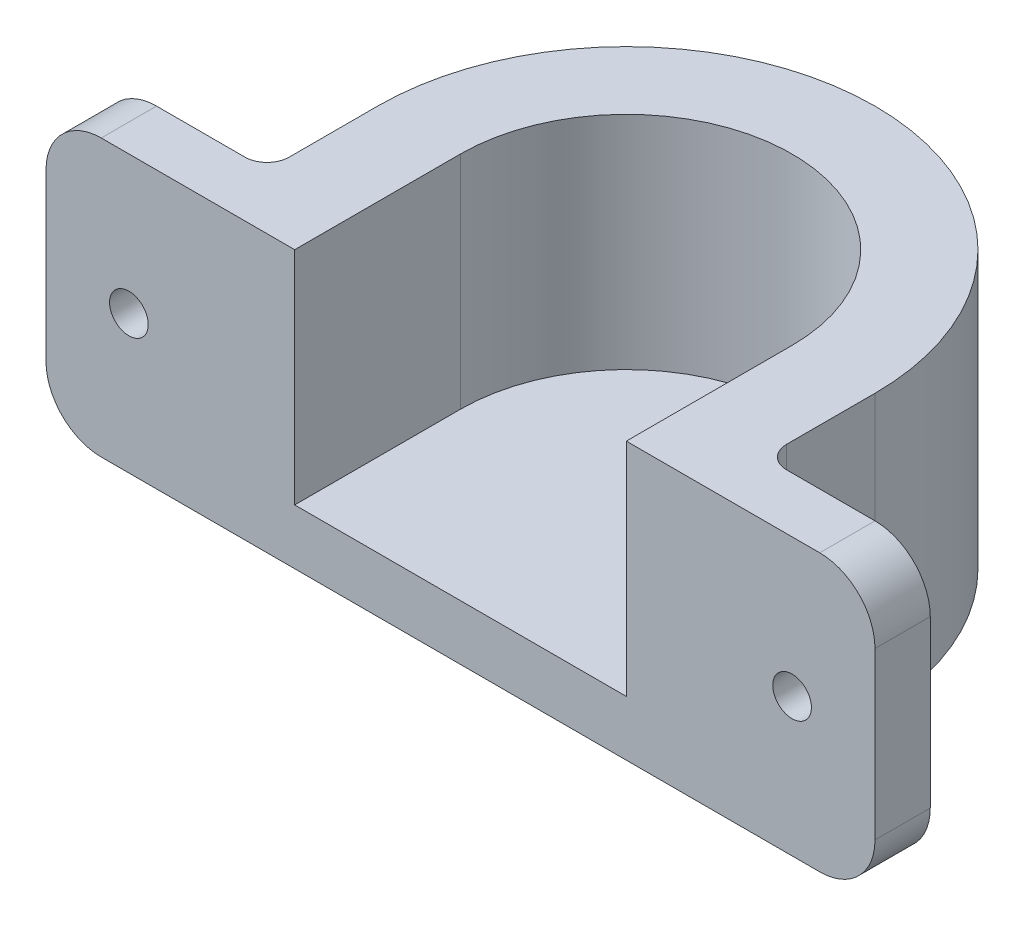
SolidWorks part; units mm, degrees
ref_plane "Front Plane" through (0, 0, 0) normal (0, 0, 1) x (1, 0, 0)
ref_plane "Top Plane" through (0, 0, 0) normal (0, 1, 0) x (1, 0, 0)
ref_plane "Right Plane" through (0, 0, 0) normal (1, 0, 0) x (0, 0, -1)
sketch "Sketch1" plane through (0, 0, 0) normal (0, 1, 0) x (1, 0, 0)
  line L0 (-7.5, 0) -> (-7.5, -10)
  line L1 (-7.5, -10) -> (-22.5, -10)
  line L2 (-22.5, -10) -> (-22.5, -15)
  line L3 (-22.5, -15) -> (0, -15)
  line L4 (0, -15) -> (0, 0)
  line L5 (-7.5, 0) -> (0, 0) construction
  line L6 (15, 0) -> (30, 0) construction
  line L7 (30, 0) -> (37.5, 0) construction
  line L8 (0, 0) -> (15, 0) construction
  line L9 (30, 0) -> (30, -15)
  line L10 (30, -15) -> (52.5, -15)
  line L11 (52.5, -15) -> (52.5, -10)
  line L12 (52.5, -10) -> (37.5, -10)
  line L13 (37.5, -10) -> (37.5, 0)
  arc A0 (-7.5, 0) -> (37.5, 0) centre (15, 0) cw
  arc A1 (0, 0) -> (30, 0) centre (15, 0) cw
  dimension "D1" = 15
  dimension "D2" = 7.5
  dimension "D3" = 5
  dimension "D4" = 15
  dimension "D5" = 15
extrude "Boss-Extrude1" add sketch "Sketch1" along normal blind 25
sketch "Sketch4" plane through (0, 0, 10) normal (0, 0, -1) x (-1, 0, 0)
  line L0 (-52.5, 12.5) -> (-37.5, 12.5) construction
  line L1 (-52.5, 25) -> (-52.5, 0) construction
  line L2 (-37.5, 25) -> (-37.5, 0) construction
  line L3 (-15, 25) -> (-15, 0) construction
  line L4 (7.5, 25) -> (-37.5, 25) construction
  line L5 (-37.5, 0) -> (7.5, 0) construction
  circle A0 centre (-45, 12.5) radius 1.75
  circle A1 centre (15, 12.5) radius 1.75
  dimension "D1" = 3.5
  dimension "D2" = 30
extrude "Cut-Extrude1" cut sketch "Sketch4" against normal through all
fillet "Fillet1" radius 5 4 edges at (52.5, 25, 12.5) (52.5, 0, 12.5) (-22.5, 25, 12.5) (-22.5, 0, 12.5)
fillet "Fillet2" radius 2 2 edges at (37.5, 12.5, 10) (-7.5, 12.5, 10)
sketch "Sketch5" plane through (0, 0, 15) normal (0, 0, 1) x (1, 0, 0)
  line L0 (30, 25) -> (30, 0) construction
  line L1 (0, 0) -> (30, 0)
  line L2 (0, 0) -> (0, 5)
  line L3 (0, 5) -> (30, 5)
  line L4 (30, 0) -> (30, 5)
  dimension "D1" = 5
extrude "Boss-Extrude2" add sketch "Sketch5" against normal blind 31
equation "\"D5@Sketch1\" = \"Diamter\" / 2"
equation "\"D1@Sketch1\" = \"Diamter\" / 2"
equation "\"Diamter\"= 30"
